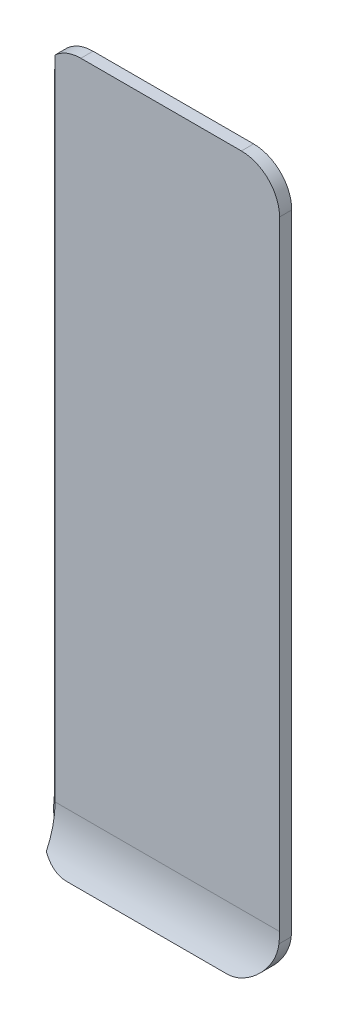
SolidWorks part; units mm, degrees
ref_plane "Front Plane" through (0, 0, 0) normal (0, 0, 1) x (1, 0, 0)
ref_plane "Top Plane" through (0, 0, 0) normal (0, 1, 0) x (1, 0, 0)
ref_plane "Right Plane" through (0, 0, 0) normal (1, 0, 0) x (0, 0, -1)
sketch "Sketch1" plane through (0, 0, 0) normal (0, 0, 1) x (1, 0, 0)
  line L1 (100, 0) -> (521, 0)
  line L2 (0, 100) -> (0, 1750)
  line L3 (100, 1850) -> (521, 1850)
  line L4 (621, 100) -> (621, 1750)
  arc A0 (100, 0) -> (0, 100) centre (100, 100) cw
  arc A1 (521, 0) -> (621, 100) centre (521, 100) ccw
  arc A2 (521, 1850) -> (621, 1750) centre (521, 1750) cw
  arc A3 (0, 1750) -> (100, 1850) centre (100, 1750) cw
  point P5 (0, 0)
  point P8 (0, 0)
  point P11 (621, 0)
  point P14 (621, 1850)
  dimension "D3" = 100
  dimension "D1" = 1850
  dimension "D2" = 621
extrude "Boss-Extrude1" add sketch "Sketch1" along normal blind 70
sketch "Sketch2" plane through (0, 0, 0) normal (-1, 0, 0) x (0, 0, 1)
  line L1 (70, 1850) -> (0, 1850) construction
  line L2 (32, 1850) -> (32, 127.4469)
  line L3 (70, 0) -> (32.6985, 0)
  line L4 (0, 1750) -> (0, 100) construction
  line L6 (70, 0) -> (0, 0) construction
  line L7 (0, 127.4469) -> (0, 0)
  line L8 (0, 0) -> (32.6985, 0)
  line L9 (70, 0) -> (70, 1850)
  line L10 (70, 1850) -> (32, 1850)
  arc A0 (32, 127.4469) -> (70, 0) centre (264.72, 127.4469) ccw
  arc A1 (32.6985, 0) -> (0, 127.4469) centre (264.72, 127.4469) cw
  point P0 (70, 0)
  line M8 (0, 100) -> (70, 100)
  line M9 (70, 100) -> (70, 1750)
  line M10 (70, 1750) -> (0, 1750)
  dimension "D2" = 264.72
  dimension "D1" = 32
extrude "Cut-Extrude1" cut sketch "Sketch2" against normal through all contours L8 A1 L7 M8 | A0 L9 M8 | L2 A0 M8 M9 M10 | L9 L10 L2 A0 | A1 L7 L8 region at (0, 925.1937, 51.0044) region at (0, 63.2656, 56.2467) region at (0, 30.721, 9.7864)
sketch "Sketch4" plane through (0, 0, 0) normal (-1, 0, 0) x (0, 0, 1)
  line L0 (32, 1850) -> (0, 1850) construction
  line L1 (1, 1850) -> (32, 1850)
  line L2 (1, 1850) -> (1, 127.4469)
  line L4 (32, 1850) -> (32, 127.4469)
  line L5 (70, 0) -> (32.6985, 0) construction
  line L6 (33.8401, 0) -> (70, 0)
  line L7 (0, 1850) -> (0, 1750) construction
  arc A0 (1, 127.4469) -> (33.8401, 0) centre (264.72, 127.4469) ccw
  arc A1 (1.4267, 100) -> (32.6985, 0) centre (264.72, 127.4469) ccw construction
  arc A2 (32, 127.4469) -> (70, 0) centre (264.72, 127.4469) ccw
  dimension "D1" = 1
extrude "Cut-Extrude2" cut sketch "Sketch4" against normal blind 32.5
